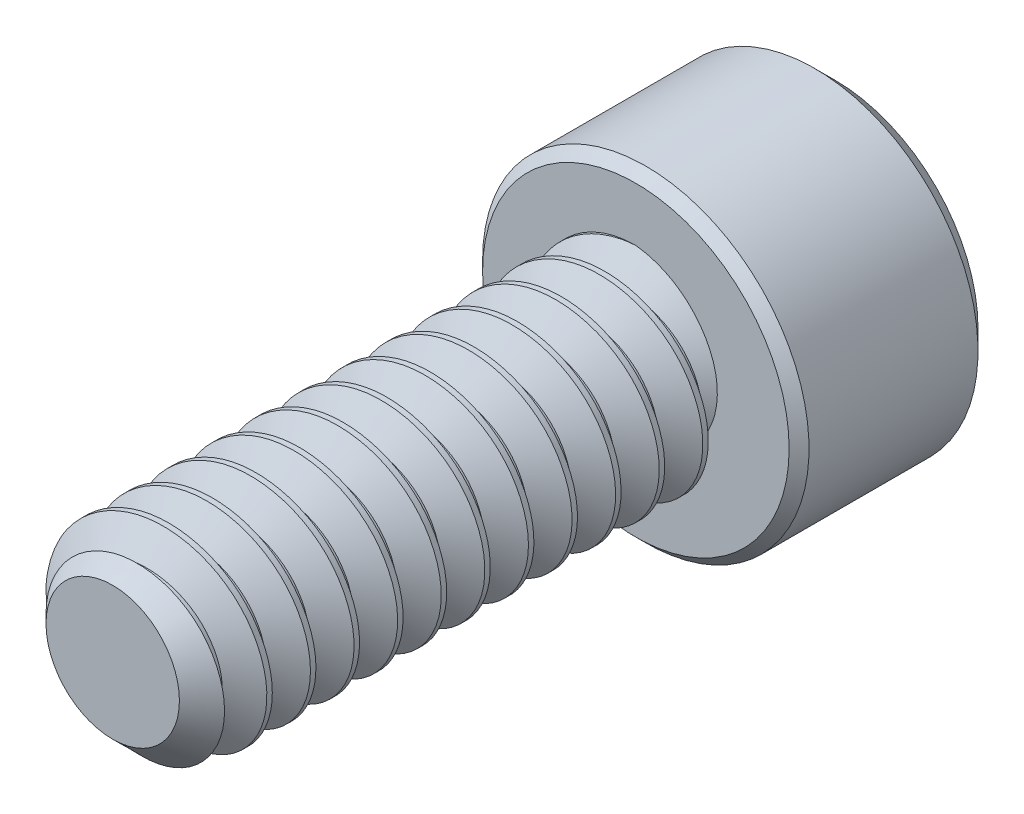
SolidWorks part; units mm, degrees
material "Plain Carbon Steel"
ref_plane "Front Plane" through (0, 0, 0) normal (0, 0, 1) x (1, 0, 0)
ref_plane "Top Plane" through (0, 0, 0) normal (0, 1, 0) x (1, 0, 0)
ref_plane "Right Plane" through (0, 0, 0) normal (1, 0, 0) x (0, 0, -1)
sketch "Sketch1" plane through (0, 0, 0) normal (0, 0, 1) x (1, 0, 0)
  line L0 (0, 2.413) -> (0, -2.413) construction
  circle A0 centre (0, 0) radius 2.413
  dimension "OD" = 4.826
extrude "Extrude1" add sketch "Sketch1" against normal blind 12.7
sketch "Sketch2" plane through (0, 0, 0) normal (0, 0, 1) x (1, 0, 0)
  circle A0 centre (0, 0) radius 2.413 construction
  circle A1 centre (0, 0) radius 2.413
curve "Helix/Spiral1" pitch 1.0583 height 13.7583 turns 13 parameters "pitch"=1.0583
chamfer "Chamfer3" distance 0.7937 angle 45 1 edges at (2.413, 0, 0)
sketch "Sketch3" plane through (0, 0, 0) normal (1, 0, 0) x (0, 0, -1)
  line L0 (-0.926, 2.413) -> (-0.5292, 1.7256)
  line L1 (-0.5292, 1.7256) -> (-0.3969, 1.7256)
  line L2 (-0.3969, 1.7256) -> (0, 2.413)
  line L3 (-0.926, 2.413) -> (0, 2.413)
  line L4 (-0.463, 2.413) -> (-0.463, 1.7256) construction
  line L5 (-0.7276, 2.0693) -> (-0.1984, 2.0693) construction
  line L6 (0, 2.413) -> (0, -2.413) construction
  dimension "D1" = 0.1323
  dimension "D2" = 0.5292
  dimension "D3" = 60
sweep "Cut-Sweep1" cut profiles "Sketch3" path "Helix/Spiral1"
sketch "Sketch6" plane through (0, 0, -12.7) normal (0, 0, -1) x (-1, 0, 0)
  circle A0 centre (0, 0) radius 3.9624
  dimension "head dia" = 7.9248
extrude "Extrude2" add sketch "Sketch6" along normal blind 4.826
sketch "Sketch7" plane through (0, 0, -17.526) normal (0, 0, -1) x (-1, 0, 0)
  line L1 (0, 2.2914) -> (-1.9844, 1.1457)
  line L2 (-1.9844, 1.1457) -> (-1.9844, -1.1457)
  line L3 (-1.9844, -1.1457) -> (0, -2.2914)
  line L4 (0, -2.2914) -> (1.9844, -1.1457)
  line L5 (1.9844, -1.1457) -> (1.9844, 1.1457)
  line L6 (1.9844, 1.1457) -> (0, 2.2914)
  circle A0 centre (0, 0) radius 1.9844 construction
  dimension "hex dia" = 3.9688
extrude "Cut-Extrude1" cut sketch "Sketch7" against normal blind 2.9766
sketch "Sketch8" plane through (0, 0, -17.526) normal (0, 0, -1) x (-1, 0, 0)
  circle A0 centre (0, 0) radius 2.2914
extrude "Cut-Extrude2" cut sketch "Sketch8" against normal blind 0.4826 draft 45
chamfer "Chamfer1" distance 0.4826 angle 45 1 edges at (-3.9624, 0, -17.526)
chamfer "Chamfer2" distance 0.2413 angle 45 1 edges at (-3.9624, 0, -12.7)
sketch "Sketch9" plane through (0, 0, 0) normal (1, 0, 0) x (0, 0, -1)
  line L0 (0, 2.413) -> (0, -2.413) construction
  line L1 (5.8208, 2.413) -> (5.8208, -2.413) construction
  line L2 (12.7, 3.9624) -> (12.7, -3.9624) construction
  line L3 (17.526, 3.9624) -> (17.526, -3.9624) construction
  line L4 (17.526, 0) -> (0, 0) construction
  dimension "D1" = 5.8208
  dimension "D2" = 4.826
  dimension "D3" = 7.9248
  dimension "D4" = 12.7
equation "\"D3@Helix/Spiral1\" = \"screw length@Extrude1\"+\"pitch@Helix/Spiral1\""
equation "\"D1@Sketch3\" = \"pitch@Helix/Spiral1\"*.125"
equation "\"D2@Sketch3\" = \"pitch@Helix/Spiral1\"*.5"
equation "\"D1@Cut-Extrude1\" = \"hex dia@Sketch7\"*.75"
equation "\"D1@Chamfer1\" = \"head depth@Extrude2\"/10"
equation "\"D1@Sketch9\" = \"pitch@Helix/Spiral1\"*5.5"
equation "\"D1@Chamfer2\" = \"D1@Chamfer1\"/2"
equation "\"D1@Cut-Extrude2\" = \"D1@Chamfer2\"*2"
equation "\"D1@Chamfer3\" = \"pitch@Helix/Spiral1\"*.750"
equation "\"D2@Sketch9\" = \"head depth@Extrude2\""
equation "\"D3@Sketch9\" = \"head dia@Sketch6\""
equation "\"D4@Sketch9\" = \"screw length@Extrude1\""
